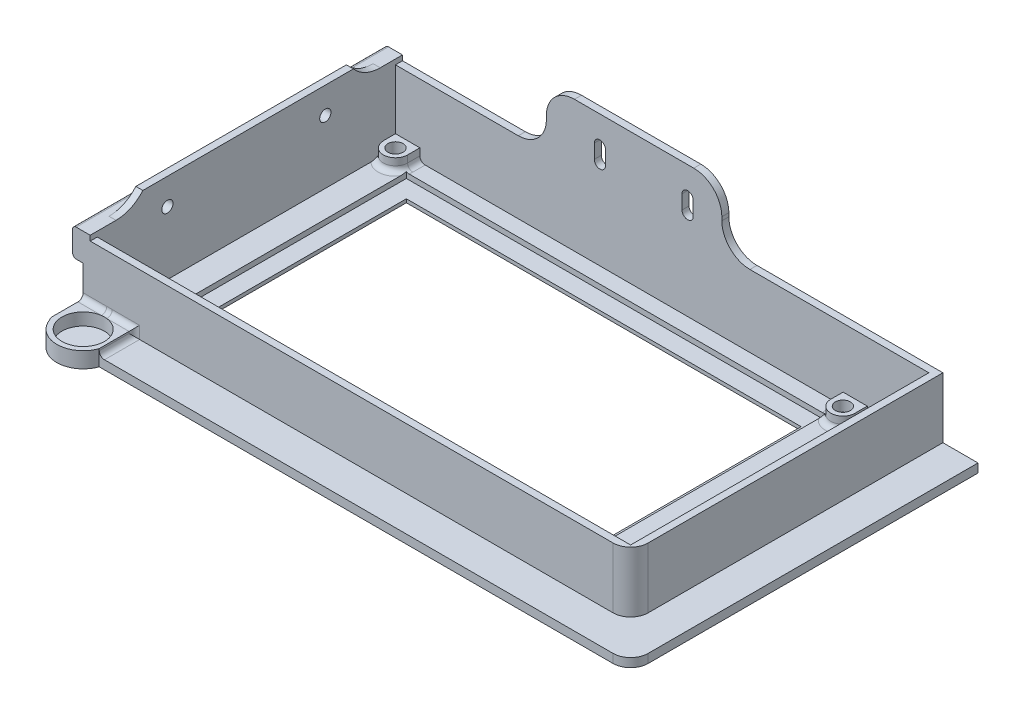
SolidWorks part; units mm, degrees
ref_plane "Alzado" through (0, 0, 0) normal (0, 0, 1) x (1, 0, 0)
ref_plane "Planta" through (0, 0, 0) normal (0, 1, 0) x (1, 0, 0)
ref_plane "Vista lateral" through (0, 0, 0) normal (1, 0, 0) x (0, 0, -1)
sketch "Croquis1" plane through (0, 0, 0) normal (0, 1, 0) x (1, 0, 0)
  line L1 (0, 0) -> (152, 0)
  line L2 (0, 0) -> (0, 85)
  line L3 (0, 85) -> (152, 85)
  line L4 (152, 0) -> (152, 85)
  dimension "D1" = 152
  dimension "D2" = 85
extrude "Saliente-Extruir1" add sketch "Croquis1" along normal blind 1.5
sketch "Croquis2" plane through (0, 1.5, 0) normal (0, 1, 0) x (1, 0, 0)
  line L0 (154, 87) -> (-2, 87)
  line L1 (-2, 87) -> (-2, -2)
  line L2 (-2, -2) -> (154, -2)
  line L3 (154, -2) -> (154, 87)
  line L4 (0, 85) -> (0, 0)
  line L5 (0, 0) -> (152, 0)
  line L6 (152, 0) -> (152, 85)
  line L7 (152, 85) -> (0, 85)
  line L8 (0, 85) -> (0, 0)
  line L9 (0, 0) -> (152, 0)
  line L10 (152, 0) -> (152, 85)
  line L11 (152, 85) -> (0, 85)
  dimension "D1" = 0
  dimension "D2" = 2
extrude "Saliente-Extruir3" add sketch "Croquis2" against normal up to surface (1.5 mm away) and the other way blind 5 up to face at (76, 0, -42.5)
sketch "Croquis3" plane through (0, 1.5, 0) normal (0, 1, 0) x (1, 0, 0)
  line L0 (0, 85) -> (0, 0) construction
  line L1 (152, 85) -> (0, 85) construction
  line L2 (76, 85) -> (76, 0) construction
  line L3 (0, 0) -> (152, 0) construction
  line L4 (0, 42.5) -> (152, 42.5) construction
  line L5 (0, 85) -> (0, 0) construction
  line L6 (152, 0) -> (152, 85) construction
  line L7 (0, 0) -> (152, 0) construction
  circle A0 centre (3.5, 81.5) radius 2.75
  circle A3 centre (3.5, 3.5) radius 3.45
  circle A4 centre (131, 81.5) radius 3.45
  circle A5 centre (131, 3.5) radius 3.45
  circle A6 centre (148.4, 3.5) radius 3.45
  circle A7 centre (148.4, 81.5) radius 3.45
  dimension "D1" = 5.5
  dimension "D4" = 6.9
  dimension "D2" = 3.5
  dimension "D3" = 3.5
  dimension "D5" = 127.5
  dimension "D6" = 3.5
  dimension "D7" = 3.5
  dimension "D8" = 3.5
  dimension "D9" = 3.5
  dimension "D10" = 127.5
  dimension "D11" = 3.6
extrude "Saliente-Extruir4" add sketch "Croquis3" along normal blind 3.5
sketch "Croquis4" plane through (0, 0, 0) normal (0, -1, 0) x (1, 0, 0)
  line L0 (-2, -87) -> (-2, 2) construction
  line L1 (7.6, -80.5) -> (127.1, -80.5)
  line L2 (7.6, -80.5) -> (7.6, -2)
  line L3 (7.6, -2) -> (127.1, -2)
  line L4 (127.1, -80.5) -> (127.1, -2)
  line L5 (154, -87) -> (-2, -87) construction
  dimension "D1" = 119.5
  dimension "D2" = 78.5
  dimension "D3" = 9.6
  dimension "D4" = 6.5
extrude "Cortar-Extruir1" cut sketch "Croquis4" against normal up to surface (1.5 mm away) up to face at (148.4, 1.5, -84.95)
sketch "Croquis5" plane through (0, 5, 0) normal (0, 1, 0) x (1, 0, 0)
  circle A0 centre (131, 3.5) radius 2.15
  circle A1 centre (3.5, 3.5) radius 2.15
  circle A2 centre (3.5, 81.5) radius 2.15
  circle A3 centre (131, 81.5) radius 2.15
  circle A4 centre (148.4, 3.5) radius 2.15
  circle A5 centre (148.4, 81.5) radius 2.15
  dimension "D1" = 4.3
extrude "Cortar-Extruir2" cut sketch "Croquis5" against normal blind 3
sketch "Croquis7" plane through (0, 6.5, 0) normal (0, 1, 0) x (1, 0, 0)
  line L0 (-2, -2) -> (154, -2) construction
  line L1 (0, 0) -> (152, 0) construction
  line L2 (0, 85) -> (0, 0) construction
  line L3 (-2, 87) -> (-2, -2) construction
  line L4 (152, 85) -> (0, 85) construction
  line L5 (154, 87) -> (-2, 87) construction
  line L6 (154, -2) -> (154, 87) construction
  line L7 (152, 0) -> (152, 85) construction
  line L8 (-2, -2) -> (86, -2)
  line L9 (0, 0) -> (86, 0)
  line L10 (0, 85) -> (0, 0)
  line L11 (-2, 87) -> (-2, -2)
  line L12 (152, 85) -> (0, 85)
  line L13 (154, 87) -> (-2, 87)
  line L14 (154, -2) -> (154, 87)
  line L15 (152, 0) -> (152, 85)
  line L16 (86, -2) -> (154, -2)
  line L21 (86, 0) -> (152, 0)
extrude "Saliente-Extruir5" add sketch "Croquis7" along normal blind 15.5
sketch "Croquis9" plane through (0, 22, 0) normal (0, 1, 0) x (1, 0, 0)
  line L0 (152, 85) -> (0, 85) construction
  line L1 (93, 85) -> (43, 85)
  line L2 (93, 85) -> (93, 87)
  line L3 (93, 87) -> (43, 87)
  line L4 (43, 85) -> (43, 87)
  line L5 (154, 87) -> (-2, 87) construction
  dimension "D1" = 50
  dimension "D2" = 45
extrude "Saliente-Extruir6" add sketch "Croquis9" along normal blind 17
sketch "Croquis10" plane through (0, 22, 0) normal (0, 1, 0) x (1, 0, 0)
  line L0 (0, 85) -> (0, 0) construction
  line L1 (0, 13) -> (-2, 13)
  line L2 (0, 13) -> (0, 73)
  line L3 (0, 73) -> (-2, 73)
  line L4 (-2, 13) -> (-2, 73)
  line L5 (-2, 87) -> (-2, -2) construction
  line L6 (-2, -2) -> (154, -2) construction
  dimension "D1" = 60
  dimension "D2" = 15
extrude "Saliente-Extruir7" add sketch "Croquis10" along normal blind 5
sketch "Croquis11" plane through (0, 0, 0) normal (1, 0, 0) x (0, 0, -1)
  line L0 (0, 22) -> (0, 1.5) construction
  line L1 (13, 27) -> (73, 27) construction
  circle A0 centre (20, 19.5) radius 1.6
  circle A1 centre (65, 19.5) radius 1.6
  dimension "D1" = 3.2
  dimension "D2" = 45
  dimension "D3" = 20
  dimension "D4" = 7.5
extrude "Cortar-Extruir4" cut sketch "Croquis11" against normal up to surface (2 mm away) up to face at (-2, 17.75, -42.75)
sketch "Croquis12" plane through (0, 0, -85) normal (0, 0, 1) x (1, 0, 0)
  line L0 (93, 39) -> (93, 22) construction
  line L2 (43, 39) -> (93, 39) construction
  circle A0 centre (83.25, 29) radius 1.6
  circle A1 centre (58.25, 29) radius 1.6
  dimension "D2" = 3.2
  dimension "D1" = 10
  dimension "D3" = 9.75
  dimension "D4" = 25
extrude "Cortar-Extruir5" cut sketch "Croquis12" against normal up to surface (2 mm away) up to face at (72, 20.75, -87)
fillet "Redondeo2" radius 8 4 edges at (93, 39, -86) (43, 39, -86) (43, 22, -86) (93, 22, -86)
sketch "Croquis13" plane through (0, 0, 2) normal (0, 0, 1) x (1, 0, 0)
  line L0 (-2, 22) -> (-2, 0) construction
  line L1 (-2, 4.75) -> (154, 4.75)
  line L2 (-2, 4.75) -> (-2, 2.25)
  line L3 (-2, 2.25) -> (154, 2.25)
  line L4 (154, 4.75) -> (154, 2.25)
  line L5 (154, 22) -> (154, 0) construction
  line L6 (-2, 0) -> (154, 0) construction
  dimension "D1" = 2.5
  dimension "D2" = 2.25
extrude "Saliente-Extruir8" add sketch "Croquis13" along normal blind 10
sketch "Croquis14" plane through (154, 0, 0) normal (1, 0, 0) x (0, 0, -1)
  line L0 (87, 22) -> (87, 0) construction
  line L1 (-12, 4.75) -> (87, 4.75)
  line L2 (-12, 4.75) -> (-12, 2.25)
  line L3 (-12, 2.25) -> (87, 2.25)
  line L4 (87, 4.75) -> (87, 2.25)
  line L5 (-12, 2.25) -> (-2, 2.25) construction
extrude "Saliente-Extruir9" add sketch "Croquis14" along normal blind 10
fillet "Redondeo3" radius 5 3 edges at (154, 1.125, 2) (164, 3.5, 12) (154, 13.375, 2)
sketch "Croquis15" plane through (0, 4.75, 0) normal (0, 1, 0) x (1, 0, 0)
  line L4 (-2, -2) -> (149, -2) construction
  line L5 (-2, -12) -> (-2, -2) construction
  circle A0 centre (5.5, -9.5) radius 7.5
  dimension "D1" = 15
extrude "Saliente-Extruir10" add sketch "Croquis15" against normal up to surface (2.5 mm away) up to face at (117.7589, 2.25, -17.4911)
sketch "Croquis16" plane through (0, 4.75, 0) normal (0, 1, 0) x (1, 0, 0)
  arc A1 (-1.5711, -12) -> (12.5711, -12) centre (5.5, -9.5) ccw construction
  arc A3 (-1.5711, -12) -> (12.5711, -12) centre (5.5, -9.5) ccw construction
  circle A4 centre (5.5, -9.5) radius 6.05
  dimension "D1" = 12.1
extrude "Cortar-Extruir6" cut sketch "Croquis16" against normal blind 1.5
sketch "Croquis17" plane through (0, 0, 0) normal (0, -1, 0) x (1, 0, 0)
  line L0 (127.1, -2) -> (7.6, -2) construction
  line L1 (127.1, -80.5) -> (127.1, -2) construction
  line L2 (7.6, -2) -> (7.6, -80.5) construction
  line L3 (7.6, -80.5) -> (127.1, -80.5) construction
  line L4 (154, -87) -> (154, -3)
  line L5 (149, 2) -> (-2, 2)
  line L6 (-2, 2) -> (-2, -87)
  line L7 (-2, -87) -> (154, -87)
  line L8 (154, -87) -> (154, -3)
  line L9 (149, 2) -> (-2, 2)
  line L10 (-2, 2) -> (-2, -87)
  line L11 (-2, -87) -> (154, -87)
  line L12 (7.6, -80.5) -> (127.1, -80.5)
  line L13 (7.6, -2) -> (7.6, -80.5)
  line L14 (127.1, -80.5) -> (127.1, -2)
  line L15 (127.1, -2) -> (7.6, -2)
  arc A1 (154, -3) -> (149, 2) centre (149, -3) ccw
  arc A2 (154, -3) -> (149, 2) centre (149, -3) ccw
  dimension "D1" = 0
extrude "Saliente-Extruir11" add sketch "Croquis17" along normal blind 1
sketch "Croquis18" plane through (0, -1, 0) normal (0, -1, 0) x (1, 0, 0)
  line L0 (7.6, -2) -> (7.6, -80.5) construction
  line L1 (127.1, -80.5) -> (7.6, -80.5)
  line L2 (127.1, -80.5) -> (127.1, -75.5)
  line L3 (127.1, -75.5) -> (7.6, -75.5)
  line L4 (7.6, -80.5) -> (7.6, -75.5)
  line L6 (7.6, -2) -> (12.6, -2)
  line L7 (7.6, -2) -> (7.6, -75.5)
  line L8 (7.6, -75.5) -> (12.6, -75.5)
  line L9 (12.6, -2) -> (12.6, -75.5)
  line L10 (127.1, -2) -> (12.6, -2)
  line L11 (127.1, -2) -> (127.1, -4)
  line L12 (127.1, -4) -> (12.6, -4)
  line L13 (12.6, -2) -> (12.6, -4)
  line L14 (127.1, -4) -> (125.1, -4)
  line L15 (127.1, -4) -> (127.1, -75.5)
  line L16 (127.1, -75.5) -> (125.1, -75.5)
  line L17 (125.1, -4) -> (125.1, -75.5)
  line M11 (7.6, -80.5) -> (7.6, -2)
  line M12 (7.6, -2) -> (127.1, -2)
  line M13 (127.1, -2) -> (127.1, -80.5)
  line M14 (127.1, -80.5) -> (7.6, -80.5)
  dimension "D1" = 5
  dimension "D2" = 5
  dimension "D3" = 2
  dimension "D4" = 2
extrude "Saliente-Extruir12" add sketch "Croquis18" against normal blind 1 contours L12 L9 M13 M12 | L12 L17 L3 M13 | L3 M13 M11 M14 | L9 L3 M12 M11 region at (67.35, -1, -78) region at (126.1, -1, -39.75) region at (10.1, -1, -38.75) region at (69.85, -1, -3)
sketch "Croquis20" plane through (0, 1.5, 0) normal (0, 1, 0) x (1, 0, 0)
  circle A0 centre (3.5, 81.5) radius 2.75 construction
  circle A1 centre (3.5, 81.5) radius 2.75
  circle A2 centre (3.5, 81.5) radius 3.45
  dimension "D1" = 6.9
extrude "Saliente-Extruir19" add sketch "Croquis20" along normal up to surface (3.5 mm away) up to face at (3.5, 5, -79.35)
sketch "Croquis21" plane through (0, 1.5, 0) normal (0, 1, 0) x (1, 0, 0)
  line L0 (35, 85) -> (0, 85) construction
  line L1 (0, 85) -> (0, 73) construction
  line L2 (6.95, 85) -> (0, 85)
  line L3 (0, 85) -> (0, 81.5)
  line L5 (6.95, 81.5) -> (6.95, 85)
  line L6 (0, 0) -> (152, 0) construction
  line L7 (0, 13) -> (0, 0) construction
  line L8 (0, 0) -> (6.95, 0)
  line L9 (0, 3.5) -> (0, 0)
  line L10 (6.95, 3.5) -> (6.95, 0)
  line L11 (0.05, 3.5) -> (0, 3.5)
  line L12 (0.05, 81.5) -> (0, 81.5)
  circle A1 centre (3.5, 81.5) radius 3.45 construction
  arc A2 (6.95, 81.5) -> (0.05, 81.5) centre (3.5, 81.5) ccw
  circle A3 centre (3.5, 3.5) radius 3.45 construction
  arc A4 (0.05, 3.5) -> (6.95, 3.5) centre (3.5, 3.5) ccw
extrude "Saliente-Extruir20" add sketch "Croquis21" along normal up to surface (3.5 mm away) up to face at (3.5, 5, -1.35)
sketch "Croquis22" plane through (0, 1.5, 0) normal (0, 1, 0) x (1, 0, 0)
  line L0 (134.45, 3.5) -> (134.45, 0)
  line L1 (0, 0) -> (152, 0) construction
  line L2 (134.45, 0) -> (127.55, 0)
  line L4 (127.55, 3.5) -> (127.55, 0)
  line L5 (134.45, 81.5) -> (134.45, 85)
  line L6 (152, 85) -> (101, 85) construction
  line L7 (134.45, 85) -> (127.55, 85)
  line L8 (127.55, 85) -> (127.55, 81.5)
  circle A0 centre (131, 3.5) radius 3.45 construction
  circle A1 centre (131, 3.5) radius 3.45 construction
  arc A2 (127.55, 3.5) -> (134.45, 3.5) centre (131, 3.5) ccw
  circle A3 centre (131, 81.5) radius 3.45 construction
  circle A4 centre (131, 81.5) radius 3.45 construction
  arc A5 (134.45, 81.5) -> (127.55, 81.5) centre (131, 81.5) ccw
extrude "Saliente-Extruir21" add sketch "Croquis22" along normal up to surface (3.5 mm away) up to face at (131, 5, -1.35)
fillet "Redondeo4" radius 1.5 12 edges at (127.55, 1.5, -83.25) (134.45, 1.5, -83.25) (6.95, 1.5, -83.25) (6.95, 1.5, -1.75) (134.45, 1.5, -1.75) (127.55, 1.5, -1.75) (148.4, 1.5, -84.95) (148.4, 1.5, -6.95) (131, 1.5, -78.05) (3.5, 1.5, -78.05) (3.5, 1.5, -6.95) (131, 1.5, -6.95)
sketch "Croquis23" plane through (0, 0, -87) normal (0, 0, -1) x (-1, 0, 0)
  line L0 (-83.25, 27) -> (-83.25, 31) construction
  line L1 (-84.85, 27) -> (-84.85, 31)
  line L2 (-81.65, 27) -> (-81.65, 31)
  line L3 (-58.25, 27) -> (-58.25, 31) construction
  line L4 (-59.85, 27) -> (-59.85, 31)
  line L5 (-56.65, 27) -> (-56.65, 31)
  arc A0 (-84.85, 27) -> (-81.65, 27) centre (-83.25, 27) ccw
  arc A1 (-81.65, 31) -> (-84.85, 31) centre (-83.25, 31) ccw
  arc A2 (-59.85, 27) -> (-56.65, 27) centre (-58.25, 27) ccw
  arc A3 (-56.65, 31) -> (-59.85, 31) centre (-58.25, 31) ccw
  circle A4 centre (-83.25, 29) radius 1.6 construction
  circle A5 centre (-58.25, 29) radius 1.6 construction
  point P2 (-83.25, 29)
  point P9 (-58.25, 29)
  dimension "D1" = 2
  dimension "D2" = 2
extrude "Cortar-Extruir7" cut sketch "Croquis23" against normal up to surface (2 mm away) up to face at (84.85, 29, -85)
sketch "Croquis24" plane through (0, 4.75, 0) normal (0, 1, 0) x (1, 0, 0)
  line L1 (-2, -2) -> (149, -2) construction
  line L2 (-2, -12) -> (-2, -2) construction
  line L3 (-1.5711, -12) -> (-2, -12) construction
  line L5 (-2, -2) -> (12.5711, -2)
  line L6 (-2, -12) -> (-2, -2)
  line L7 (-1.5711, -12) -> (-2, -12)
  line L8 (12.5711, -12) -> (12.5711, -2)
  arc A0 (-1.5711, -12) -> (12.5711, -12) centre (5.5, -9.5) ccw construction
  arc A1 (-1.5711, -12) -> (12.5711, -12) centre (5.5, -9.5) ccw
  circle A2 centre (5.5, -9.5) radius 6.05 construction
  circle A3 centre (5.5, -9.5) radius 6.05
extrude "Saliente-Extruir22" add sketch "Croquis24" along normal blind 2
fillet "Redondeo5" radius 1.5 3 edges at (5.2855, 6.75, 2) (12.5711, 5.75, 2) (12.5711, 4.75, 7)
fillet "Redondeo6" radius 2 1 edges at (-2, 4.5, 12)
sketch "Croquis25" plane through (-2, 0, 0) normal (-1, 0, 0) x (0, 0, 1)
  line L0 (-65, 19.5) -> (2, 19.5) construction
  line L1 (2, 22) -> (2, 8.25) construction
  line L3 (2, 15.55) -> (-87, 15.55)
  line L4 (2, 15.55) -> (2, 23.45)
  line L5 (2, 23.45) -> (-87, 23.45)
  line L6 (-87, 15.55) -> (-87, 23.45)
  circle A0 centre (-20, 19.5) radius 1.6 construction
  circle A1 centre (-20, 19.5) radius 1.6
  circle A2 centre (-65, 19.5) radius 1.6 construction
  circle A3 centre (-65, 19.5) radius 1.6
  dimension "D1" = 7.9
  dimension "D2" = 3.95
extrude "Saliente-Extruir23" add sketch "Croquis25" along normal blind 3
sketch "Croquis26" plane through (-2, 0, 0) normal (1, 0, 0) x (0, 0, -1)
  line L4 (-2, 22) -> (13, 22)
  line L5 (13, 22) -> (13, 23.45)
  line L6 (13, 23.45) -> (-2, 23.45)
  line L7 (-2, 23.45) -> (-2, 22)
  line L8 (-2, 22) -> (13, 22)
  line L9 (13, 22) -> (13, 23.45)
  line L10 (13, 23.45) -> (-2, 23.45)
  line L11 (-2, 23.45) -> (-2, 22)
  line L12 (73, 22) -> (87, 22)
  line L13 (87, 22) -> (87, 23.45)
  line L14 (87, 23.45) -> (73, 23.45)
  line L15 (73, 23.45) -> (73, 22)
  line L16 (73, 22) -> (87, 22)
  line L17 (87, 22) -> (87, 23.45)
  line L18 (87, 23.45) -> (73, 23.45)
  line L19 (73, 23.45) -> (73, 22)
  dimension "D1" = 0
  dimension "D2" = 0
extrude "Saliente-Extruir24" add sketch "Croquis26" along normal up to surface (2 mm away) up to face at (0, 19.5, -21.6)
fillet "Redondeo7" radius 10 2 edges at (-1, 23.45, -73) (-1, 23.45, -13)
fillet "Redondeo8" radius 1 2 edges at (-5, 23.45, -42.5) (-5, 15.55, -42.5)
